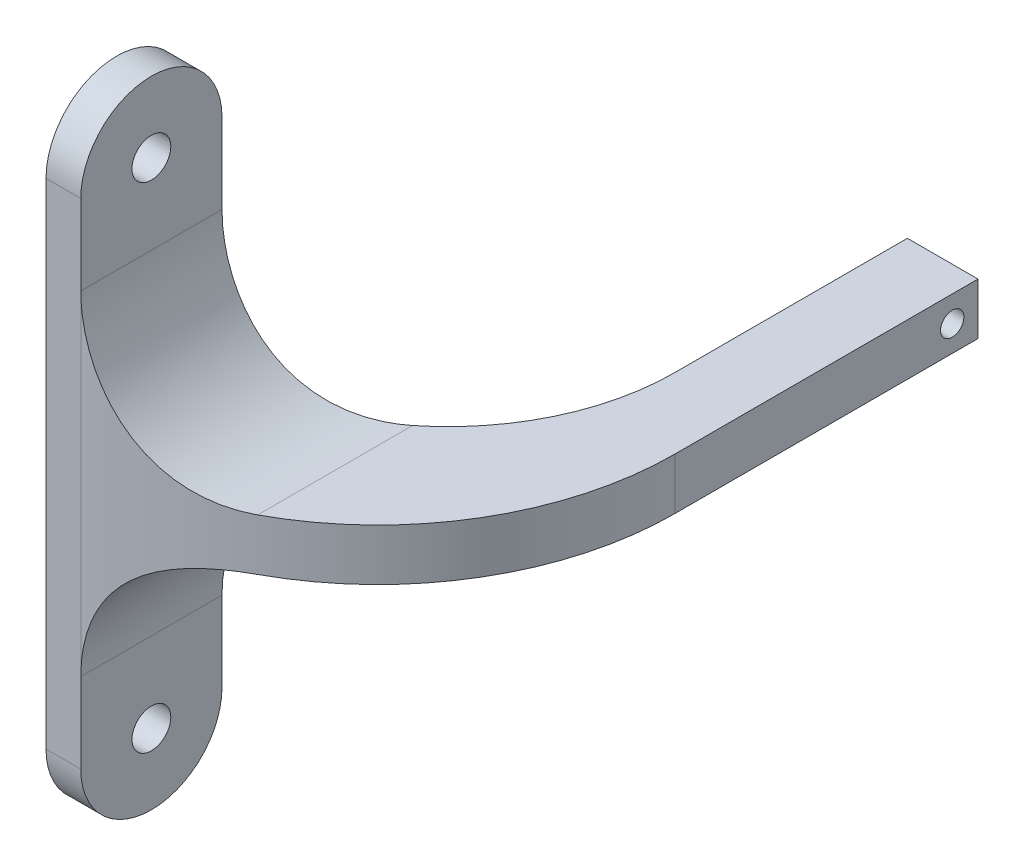
SolidWorks part; units mm, degrees
ref_plane "Front Plane" through (0, 0, 0) normal (1, 0, 0) x (0, 1, 0)
ref_plane "Top Plane" through (0, 0, 0) normal (0, 0, 1) x (0, 1, 0)
ref_plane "Right Plane" through (0, 0, 0) normal (0, 1, 0) x (-1, 0, 0)
sketch "Sketch1" plane through (0, 0, 0) normal (1, 0, 0) x (0, 1, 0)
  line L0 (-35, 0) -> (35, 0) construction
  line L1 (-35, 10) -> (35, 10)
  line L2 (-35, -10) -> (35, -10)
  arc A0 (-35, 10) -> (-35, -10) centre (-35, 0) ccw
  arc A1 (35, -10) -> (35, 10) centre (35, 0) ccw
  circle A2 centre (-35, 0) radius 2.75
  circle A3 centre (35, 0) radius 2.75
  point P3 (0, 0)
  dimension "D2" = 10
  dimension "D3" = 5.5
  dimension "D1" = 70
extrude "Boss-Extrude1" add sketch "Sketch1" along normal blind 5 from offset 3.175
sketch "Sketch5" plane through (0, 0, 0) normal (0, 1, 0) x (-1, 0, 0)
  line L0 (-40.25, -42.075) -> (-40.25, -75)
  line L1 (-40.25, -75) -> (-50.25, -75)
  line L2 (-50.25, -75) -> (-50.25, -32.075)
  line L3 (-8.175, 10) -> (-3.175, 10) construction
  line L4 (-8.175, -10) -> (-3.175, -10) construction
  line L5 (-8.175, 10) -> (-8.175, -10)
  line L6 (0, 0) -> (0, 54.8192) construction
  arc A1 (-50.25, -32.075) -> (-8.175, 10) centre (-8.175, -32.075) cw
  arc A2 (-40.25, -42.075) -> (-8.175, -10) centre (-8.175, -42.075) cw
  dimension "D1" = 10
  dimension "D2" = 65
  dimension "D3" = 80.5
extrude "Boss-Extrude2" add sketch "Sketch5" along normal mid plane 7.302
fillet "Fillet1" radius 20 2 edges at (8.175, -3.651, 0) (8.175, 3.651, 0)
sketch "Sketch6" plane through (50.25, 0, 0) normal (1, 0, 0) x (0, 1, 0)
  line L0 (-3.651, -75) -> (3.651, -67.698) construction
  line L1 (3.651, -32.075) -> (3.651, -75) construction
  line L2 (-3.651, -75) -> (3.651, -75) construction
  line L3 (3.651, -75) -> (3.651, -67.698) construction
  circle A0 centre (0, -71.349) radius 1.651
  dimension "D1" = 3.302
extrude "Cut-Extrude2" cut sketch "Sketch6" against normal through all and the other way through all
sketch "Sketch2" plane through (0, 0, 0) normal (0, 1, 0) x (-1, 0, 0)
  line L0 (-8.175, 10) -> (-3.175, 10) construction
  line L1 (-3.25, -10) -> (3.25, -10)
  line L2 (-3.25, -10) -> (-3.25, 10)
  line L3 (-3.25, 10) -> (3.25, 10)
  line L4 (3.25, -10) -> (3.25, 10)
  line L5 (-3.25, -10) -> (3.25, 10) construction
  line L6 (-3.25, 10) -> (3.25, -10) construction
  point P0 (0, 0)
  dimension "D1" = 6.5
extrude "Cut-Extrude1" cut sketch "Sketch2" against normal through all both and the other way through all
